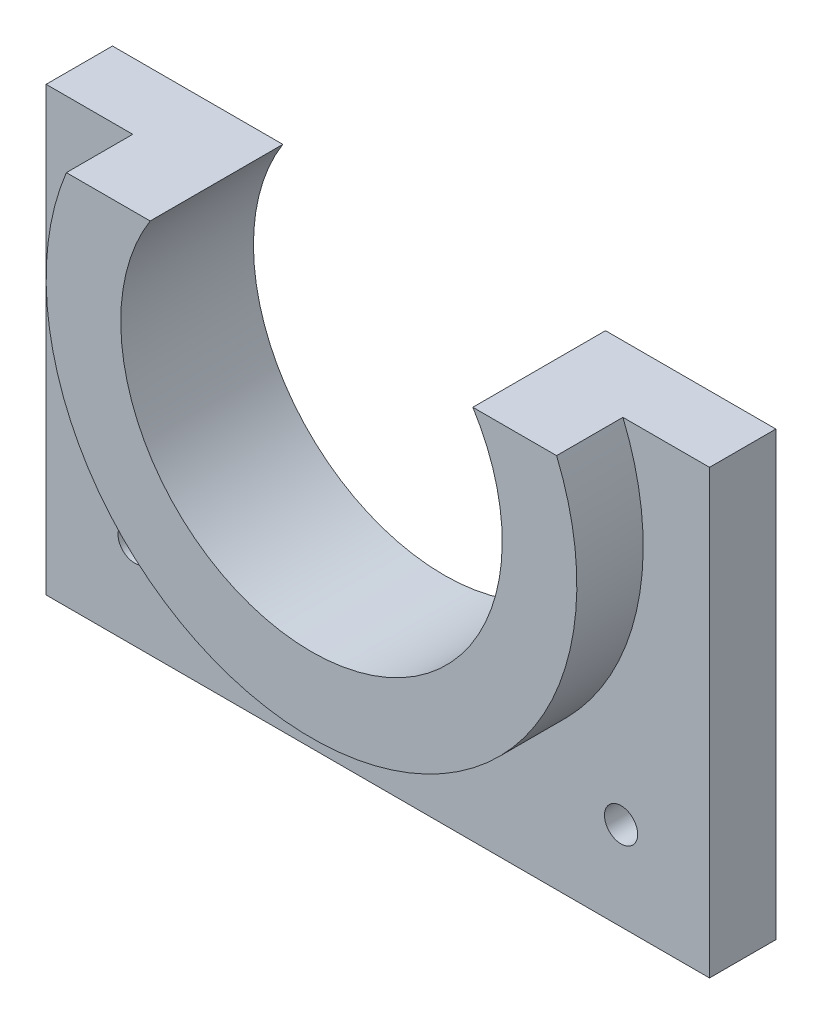
SolidWorks part; units mm, degrees
ref_plane "Front Plane" through (0, 0, 0) normal (0, 0, 1) x (1, 0, 0)
ref_plane "Top Plane" through (0, 0, 0) normal (0, 1, 0) x (1, 0, 0)
ref_plane "Right Plane" through (0, 0, 0) normal (1, 0, 0) x (0, 0, -1)
sketch "Sketch1" plane through (0, 0, 0) normal (0, 0, 1) x (1, 0, 0)
  line L0 (19.05, 57.15) -> (19.05, 31.75)
  line L1 (19.05, 31.75) -> (-19.05, 31.75)
  line L2 (-19.05, 31.75) -> (-19.05, 57.15)
  line L3 (-19.05, 57.15) -> (-9.2658, 57.15)
  line L4 (9.2658, 57.15) -> (19.05, 57.15)
  arc A1 (-9.2658, 57.15) -> (9.2658, 57.15) centre (0, 51.308) ccw
  circle A2 centre (0, 51.308) radius 10.9982 construction
  point P6 (0, 31.75)
  dimension "D4" = 10.9537
  dimension "D1" = 38.1
  dimension "D2" = 31.75
  dimension "D3" = 25.4
extrude "Boss-Extrude1" add sketch "Sketch1" along normal blind 3.81
sketch "Sketch2" plane through (0, 0, 3.81) normal (0, 0, 1) x (1, 0, 0)
  line L5 (19.05, 57.15) -> (9.2658, 57.15)
  line L6 (-9.2658, 57.15) -> (-19.05, 57.15)
  line L7 (-19.05, 57.15) -> (-19.05, 31.75)
  line L8 (-19.05, 31.75) -> (19.05, 31.75)
  line L9 (19.05, 31.75) -> (19.05, 57.15)
  line L10 (14.0758, 57.15) -> (9.2658, 57.15)
  line L11 (-9.2658, 57.15) -> (-14.0758, 57.15)
  arc A0 (14.0758, 57.15) -> (-14.0758, 57.15) centre (0, 51.308) cw
  arc A1 (-9.2658, 57.15) -> (9.2658, 57.15) centre (0, 51.308) ccw
  arc A2 (-9.2658, 57.15) -> (9.2658, 57.15) centre (0, 51.308) ccw
  dimension "D2" = 15.24
  dimension "D1" = 0
extrude "Boss-Extrude2" add sketch "Sketch2" along normal blind 3.81
sketch "Sketch3" plane through (0, 0, 3.81) normal (0, 0, 1) x (1, 0, 0)
  line L0 (0, 0) -> (0, 40.3543) construction
  line L1 (-19.05, 31.75) -> (19.05, 31.75) construction
  line L2 (-19.05, 57.15) -> (-19.05, 31.75) construction
  circle A0 centre (-13.97, 36.83) radius 0.9525
  arc A1 (-9.2658, 57.15) -> (9.2658, 57.15) centre (0, 51.308) ccw construction
  circle A2 centre (13.97, 36.83) radius 0.9525
  dimension "D1" = 1.905
  dimension "D2" = 5.08
  dimension "D3" = 5.08
extrude "Cut-Extrude1" cut sketch "Sketch3" against normal up to surface (3.81 mm away) up to face at (0, 45.884, 0)
